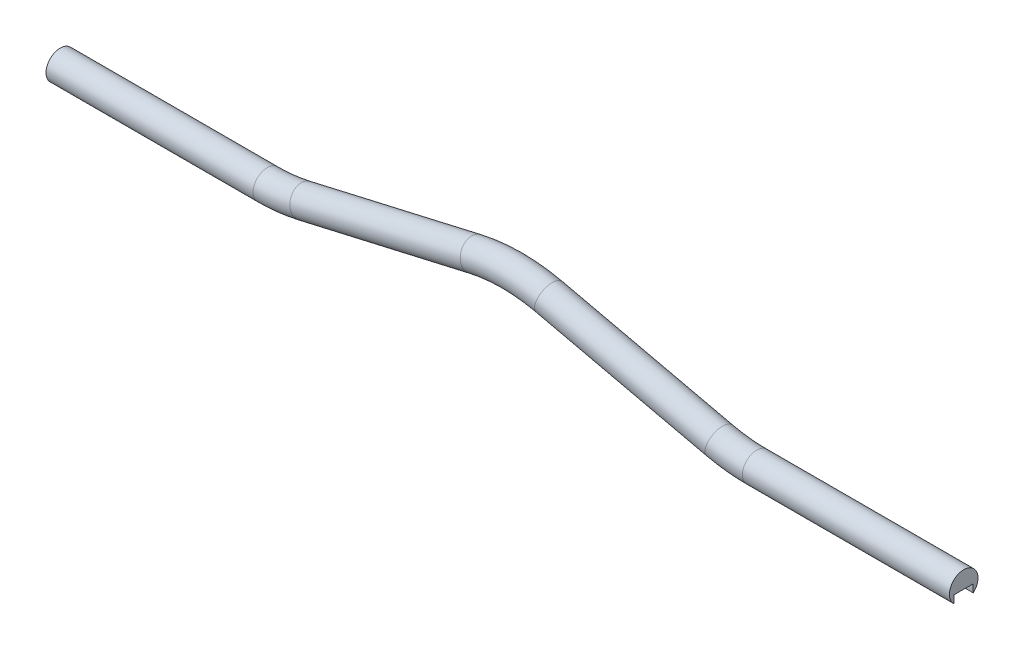
SolidWorks part; units mm, degrees
ref_plane "Front Plane" through (0, 0, 0) normal (0, 0, 1) x (1, 0, 0)
ref_plane "Top Plane" through (0, 0, 0) normal (0, 1, 0) x (1, 0, 0)
ref_plane "Right Plane" through (0, 0, 0) normal (1, 0, 0) x (0, 0, -1)
sketch "Sketch1" plane through (0, 0, 0) normal (0, 0, 1) x (1, 0, 0)
  line L0 (-475, 0) -> (-257.2802, 0)
  line L1 (-218.2217, 4.4273) -> (-39.0585, 45.5727)
  line L2 (0, 0) -> (0, 50) construction
  line L3 (218.2217, 4.4273) -> (39.0585, 45.5727)
  line L4 (475, 0) -> (257.2802, 0)
  arc A0 (257.2802, 0) -> (218.2217, 4.4273) centre (257.2802, 174.5036) cw
  arc A1 (39.0585, 45.5727) -> (-39.0585, 45.5727) centre (0, -124.5036) ccw
  arc A2 (-257.2802, 0) -> (-218.2217, 4.4273) centre (-257.2802, 174.5036) ccw
  point P7 (-475, 0)
  point P11 (237.5, 0)
  point P13 (0, 50)
  point P17 (-237.5, 0)
  point P18 (0, 0)
  dimension "D1" = 237.5
  dimension "D3" = 50
  dimension "D2" = 475
sweep "Sweep1" add path "Sketch1" circular profile diameter 30 parameters "D3"=30
sketch "Sketch26" plane through (-475, 0, 0) normal (-1, 0, 0) x (0, 0, 1)
  line L1 (-10, -27.1791) -> (10, -27.1791)
  line L2 (-10, -27.1791) -> (-10, -2.8209)
  line L3 (-10, -2.8209) -> (10, -2.8209)
  line L4 (10, -27.1791) -> (10, -2.8209)
  line L5 (-10, -27.1791) -> (10, -2.8209) construction
  line L6 (-10, -2.8209) -> (10, -27.1791) construction
  circle A0 centre (0, 0) radius 15 construction
  point P0 (0, -15)
extrude "Cut-Extrude2" cut sketch "Sketch26" against normal blind 237.5
extrude "Cut-Extrude3" cut sketch "Sketch26<2>" along normal blind 237.5 from surface starting at face at (475, -15, 0)
sketch "Sketch26<2>" plane through (-475, 0, 0) normal (-1, 0, 0) x (0, 0, 1) same geometry as "Sketch26"
